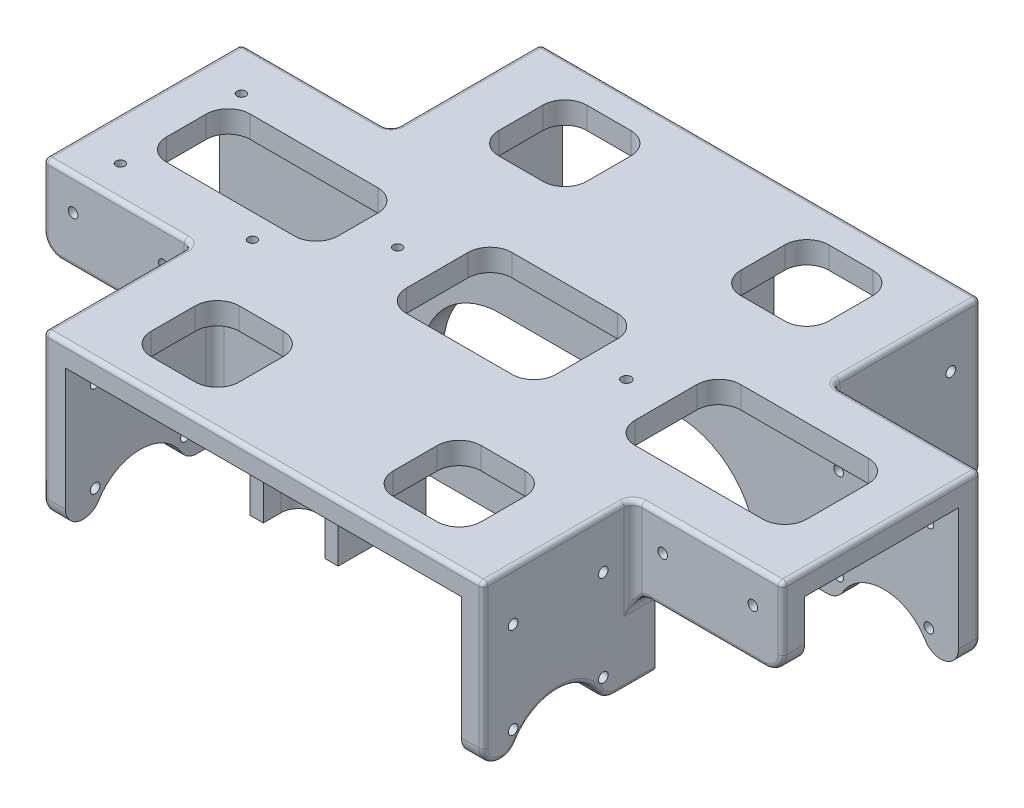
SolidWorks part; units mm, degrees
material "ABS"
ref_plane "Front Plane" through (0, 0, 0) normal (0, 0, 1) x (1, 0, 0)
ref_plane "Top Plane" through (0, 0, 0) normal (0, 1, 0) x (1, 0, 0)
ref_plane "Right Plane" through (0, 0, 0) normal (1, 0, 0) x (0, 0, -1)
sketch "Sketch1" plane through (0, 0, 0) normal (0, 1, 0) x (1, 0, 0)
  line L0 (-84, 0) -> (84, 0)
  line L5 (84, 0) -> (84, 5)
  line L6 (84, 5) -> (50, 5)
  line L7 (50, 5) -> (50, 39)
  line L8 (50, 39) -> (45, 39)
  line L9 (45, 39) -> (45, 5)
  line L10 (45, 5) -> (-45, 5)
  line L11 (-45, 5) -> (-45, 39)
  line L12 (-45, 39) -> (-50, 39)
  line L13 (-50, 39) -> (-50, 5)
  line L14 (-50, 5) -> (-84, 5)
  line L15 (-84, 5) -> (-84, 0)
  line L16 (-50, -74) -> (-50, -40)
  line L17 (-40, -35) -> (50, -35)
  line L18 (50, -40) -> (50, -74)
  line L19 (50, -74) -> (45, -74)
  line L20 (45, -74) -> (45, -40)
  line L21 (45, -40) -> (-45, -40)
  line L22 (-45, -40) -> (-45, -74)
  line L23 (-45, -74) -> (-50, -74)
  line L24 (-40, -35) -> (-84, -35)
  line L25 (-84, -35) -> (-84, -40)
  line L26 (-84, -40) -> (-50, -40)
  line L27 (50, -35) -> (84, -35)
  line L28 (84, -35) -> (84, -40)
  line L29 (84, -40) -> (50, -40)
  dimension "D1" = 5
  dimension "D2" = 90
  dimension "D3" = 34
  dimension "D4" = 34
  dimension "D5" = 5
  dimension "D6" = 5
  dimension "D7" = 5
  dimension "D8" = 5
  dimension "D9" = 34
  dimension "D10" = 34
  dimension "D11" = 5
  dimension "D12" = 34
  dimension "D13" = 5
  dimension "D14" = 90
  dimension "D15" = 35
  dimension "D16" = 34
  dimension "D17" = 34
  dimension "D18" = 34
extrude "Boss-Extrude3" add sketch "Sketch1" along normal blind 31.8
sketch "Sketch6" plane through (-50, 0, 0) normal (-1, 0, 0) x (0, 0, 1)
  line L0 (17.5, 50.2028) -> (17.5, -29.6214) construction
  line L1 (-22, -21.2285) -> (-22, 48.7432) construction
  line L2 (-52.3201, 17) -> (81.6934, 17) construction
  line L3 (-32.3501, 0) -> (-11.6499, 0)
  line L4 (-39, 0) -> (-5, 0) construction
  line L5 (-5, 31.8) -> (-5, 0) construction
  line L6 (0, 31.8) -> (0, 0) construction
  line L7 (67.3501, 0) -> (46.6499, 0)
  circle A0 centre (-32.25, 25.475) radius 1.1
  circle A3 centre (-32.25, 4.775) radius 1.1
  arc A10 (-32.3501, 0) -> (-11.6499, 0) centre (-22, -3.725) cw
  arc A11 (67.3501, 0) -> (46.6499, 0) centre (57, -3.725) ccw
  circle A12 centre (-11.75, 4.775) radius 1.1
  circle A13 centre (-11.75, 25.475) radius 1.1
  circle A14 centre (46.75, 4.775) radius 1.1
  circle A15 centre (46.75, 25.475) radius 1.1
  circle A16 centre (67.25, 25.475) radius 1.1
  circle A17 centre (67.25, 4.775) radius 1.1
  dimension "D1" = 2.2
  dimension "D2" = 12.225
  dimension "D3" = 8.475
  dimension "D8" = 8.5
  dimension "D7" = 11
  dimension "D11" = 2.2
  dimension "D4" = 17
  dimension "D5" = 17
  dimension "D6" = 17.5
  dimension "D9" = 20.5
  dimension "D10" = 20.5
extrude "Cut-Extrude2" cut sketch "Sketch6" against normal through all
sketch "Sketch9" plane through (0, 31.8, 0) normal (0, 1, 0) x (1, 0, 0)
  line L0 (0, 5) -> (0, 0) construction
  line L17 (-45, 39) -> (45, 39)
  line L23 (-45, -40) -> (45, -40) construction
  line L25 (45, -74) -> (-45, -74)
  line L35 (0, -35.0898) -> (0, -40) construction
  line L36 (0, -74) -> (0, -88.5709) construction
  line L37 (-50, 39) -> (-45, 39)
  line L38 (45, 39) -> (50, 39)
  line L39 (-84, 5) -> (-84, 0)
  line L40 (-50, -74) -> (-45, -74)
  line L41 (45, -74) -> (50, -74)
  line L42 (84, 0) -> (84, 5)
  line L43 (-84, 0) -> (-84, -40)
  line L47 (84, 0) -> (84, -40)
  line L49 (-50, 39) -> (-50, 5)
  line L50 (-50, 5) -> (-84, 5)
  line L51 (-84, -40) -> (-50, -40)
  line L52 (-50, -40) -> (-50, -74)
  line L53 (50, -74) -> (50, -40)
  line L54 (50, -40) -> (84, -40)
  line L55 (84, 5) -> (50, 5)
  line L56 (50, 5) -> (50, 39)
extrude "Boss-Extrude5" add sketch "Sketch9" along normal blind 5
sketch "Sketch18" plane through (0, 0, 40) normal (0, 0, 1) x (1, 0, 0)
  line L0 (-84, 0) -> (-84, 18.4)
  line L1 (-84, 36.8) -> (-84, 0) construction
  line L2 (-84, 18.4) -> (-50, 18.4)
  line L3 (-50, 36.8) -> (-50, 0) construction
  line L4 (-50, 18.4) -> (-50, 0)
  line L5 (-50, 0) -> (-84, 0)
  line L6 (50, 0) -> (50, 18.4)
  line L7 (50, 36.8) -> (50, 0) construction
  line L8 (50, 18.4) -> (84, 18.4)
  line L9 (84, 36.8) -> (84, 0) construction
  line L10 (84, 18.4) -> (84, 0)
  line L11 (84, 0) -> (50, 0)
extrude "Cut-Extrude6" cut sketch "Sketch18" against normal blind 10
sketch "Sketch7" plane through (0, 0, -5) normal (0, 0, -1) x (-1, 0, 0)
  line L0 (0, 73.1481) -> (0, -54.2695) construction
  line L1 (-67, -37.1805) -> (-67, 67.9015) construction
  line L2 (-84, 36.8) -> (-84, 0) construction
  line L3 (-110.062, 17) -> (103.6114, 17) construction
  line L4 (-84, 0) -> (-50, 0) construction
  line L5 (-67, 71.1805) -> (-67, -33.9015) construction
  line L8 (-77.3501, 0) -> (-56.6499, 0)
  line L9 (77.3501, 0) -> (56.6499, 0)
  circle A3 centre (-77.25, 4.775) radius 1.1
  arc A10 (-77.3501, 0) -> (-56.6499, 0) centre (-67, -3.725) cw
  arc A11 (77.3501, 0) -> (56.6499, 0) centre (67, -3.725) ccw
  circle A12 centre (-77.25, 25.475) radius 1.1
  circle A13 centre (-56.75, 25.475) radius 1.1
  circle A14 centre (-56.75, 4.775) radius 1.1
  circle A15 centre (56.75, 4.775) radius 1.1
  circle A16 centre (77.25, 4.775) radius 1.1
  circle A17 centre (56.75, 25.475) radius 1.1
  circle A18 centre (77.25, 25.475) radius 1.1
  dimension "D3" = 2.2
  dimension "D5" = 12.225
  dimension "D6" = 11
  dimension "D8" = 10.25
  dimension "D9" = 10.25
  dimension "D10" = 2.2
  dimension "D1" = 17
  dimension "D2" = 17
  dimension "D4" = 8.475
  dimension "D7" = 8.5
sketch "Sketch19" plane through (0, 36.8, 0) normal (0, 1, 0) x (1, 0, 0)
  circle A0 centre (-26, -17.5) radius 1
  circle A1 centre (26, -17.5) radius 1.1
  dimension "D1" = 26
  dimension "D2" = 26
  dimension "D3" = 2
  dimension "D4" = 2.2
  dimension "D5" = 17.5
  dimension "D6" = 17.5
extrude "Cut-Extrude7" cut sketch "Sketch19" against normal blind 10
sketch "Sketch20" plane through (0, 31.8, 0) normal (0, -1, 0) x (1, 0, 0)
  line L0 (-84, 0) -> (84, 0) construction
  line L1 (-84, 0) -> (-84, 35) construction
  circle A0 centre (-74, 32.5) radius 1
  circle A1 centre (-74, 5) radius 1
  circle A2 centre (-44, 32.5) radius 1
  dimension "D1" = 30
  dimension "D2" = 27.5
  dimension "D3" = 2
  dimension "D4" = 2
  dimension "D5" = 2
  dimension "D6" = 5
  dimension "D7" = 10
  dimension "D8" = 10
  dimension "D9" = 27.5
extrude "Cut-Extrude8" cut sketch "Sketch20" against normal blind 10
extrude "Cut-Extrude9" cut sketch "Sketch7" against normal blind 10
sketch "Sketch21" plane through (0, 0, 40) normal (0, 0, 1) x (1, 0, 0)
  line L0 (-67, 62.4596) -> (-67, -41.6657) construction
  line L1 (0, 68.3238) -> (0, -51.3917) construction
  line L3 (-101.9799, 17) -> (93.8272, 17) construction
  line L4 (-84, 0) -> (-77.3501, 0) construction
  circle A0 centre (-77.25, 29.225) radius 1.1
  circle A1 centre (-56.75, 29.225) radius 1.1
  circle A2 centre (56.75, 29.225) radius 1.1
  circle A3 centre (77.25, 29.225) radius 1.1
  dimension "D1" = 2.2
  dimension "D2" = 12.225
  dimension "D3" = 17
  dimension "D4" = 20.5
  dimension "D5" = 17
extrude "Cut-Extrude10" cut sketch "Sketch21" against normal blind 10
sketch "Sketch23" plane through (0, 31.8, 0) normal (0, -1, 0) x (1, 0, 0)
  line L0 (-45, 74) -> (45, 74) construction
  line L1 (-7, 59) -> (7, 59)
  line L2 (-7, 59) -> (-7, 55)
  line L3 (-7, 55) -> (7, 55)
  line L4 (7, 59) -> (7, 55)
  line L5 (-7, 67) -> (-10, 67)
  line L6 (-7, 67) -> (-7, 47)
  line L7 (-7, 47) -> (-10, 47)
  line L8 (-10, 67) -> (-10, 47)
  line L9 (7, 67) -> (10, 67)
  line L10 (7, 67) -> (7, 47)
  line L11 (7, 47) -> (10, 47)
  line L12 (10, 67) -> (10, 47)
  line L13 (0, -20.24) -> (0, 20.24) construction
  line L14 (-84, 17.5) -> (84, 17.5) construction
  line L15 (-84, 0) -> (-84, 35) construction
  line L16 (84, 35) -> (84, 0) construction
  line L17 (7, -12) -> (10, -12)
  line L18 (10, -32) -> (10, -12)
  line L19 (7, -32) -> (10, -32)
  line L20 (7, -32) -> (7, -12)
  line L21 (-7, -20) -> (7, -20)
  line L22 (7, -24) -> (7, -20)
  line L23 (-7, -24) -> (7, -24)
  line L24 (-7, -24) -> (-7, -20)
  line L25 (-7, -12) -> (-10, -12)
  line L26 (-10, -32) -> (-10, -12)
  line L27 (-7, -32) -> (-10, -32)
  line L28 (-7, -32) -> (-7, -12)
  point P14 (0, 55)
  dimension "D1" = 20
  dimension "D2" = 3
  dimension "D3" = 0
  dimension "D4" = 0
  dimension "D5" = 20
  dimension "D6" = 3
  dimension "D7" = 4
  dimension "D8" = 8
  dimension "D9" = 7
  dimension "D10" = 7
  dimension "D11" = 20
extrude "Boss-Extrude6" add sketch "Sketch23" along normal blind 15 contours L5 L8 L7 L6 L2 | L4 L1 L2 L3 | L12 L9 L10 L4 L11 | L27 L28 L24 L25 L26 | L24 L23 L20 L21 | L20 L19 L18 L17 region at (0, 31.8, 57) region at (-8.5, 31.8, 57) region at (8.5, 31.8, 57) region at (8.5, 31.8, -22) region at (0, 31.8, -22) region at (-8.5, 31.8, -22)
sketch "Sketch24" plane through (0, 0, 40) normal (0, 0, 1) x (1, 0, 0)
  line L0 (-20, 0) -> (20, 0) construction
  line L1 (-45, 0) -> (45, 0) construction
  line L2 (-20, 18) -> (20, 18)
  line L3 (-20, -18) -> (20, -18)
  arc A0 (-20, 18) -> (-20, -18) centre (-20, 0) ccw
  arc A1 (20, -18) -> (20, 18) centre (20, 0) ccw
  point P4 (0, 0)
  dimension "D1" = 40
  dimension "D2" = 18
extrude "Cut-Extrude11" cut sketch "Sketch24" against normal blind 46
sketch "Sketch25" plane through (0, 31.8, 0) normal (0, -1, 0) x (1, 0, 0)
  line L0 (-84, 0) -> (-84, 35) construction
  line L1 (-12, 29.5) -> (12, 29.5)
  line L2 (-17, 24.5) -> (-17, 10.5)
  line L3 (-12, 5.5) -> (12, 5.5)
  line L4 (17, 24.5) -> (17, 10.5)
  line L5 (40, 29.5) -> (69, 29.5)
  line L6 (35, 24.5) -> (35, 10.5)
  line L7 (40, 5.5) -> (69, 5.5)
  line L8 (74, 24.5) -> (74, 10.5)
  line L9 (-69, 27) -> (-40, 27)
  line L10 (-74, 22) -> (-74, 13)
  line L11 (-69, 8) -> (-40, 8)
  line L12 (-35, 22) -> (-35, 13)
  line L13 (-32.5, 67) -> (-22.5, 67)
  line L14 (-37.5, 62) -> (-37.5, 52)
  line L15 (-32.5, 47) -> (-22.5, 47)
  line L16 (-17.5, 62) -> (-17.5, 52)
  line L17 (22.5, 67) -> (32.5, 67)
  line L18 (17.5, 62) -> (17.5, 52)
  line L19 (22.5, 47) -> (32.5, 47)
  line L20 (37.5, 62) -> (37.5, 52)
  line L21 (-32.5, -12) -> (-22.5, -12)
  line L22 (-37.5, -17) -> (-37.5, -27)
  line L23 (-32.5, -32) -> (-22.5, -32)
  line L24 (-17.5, -17) -> (-17.5, -27)
  line L25 (22.5, -12) -> (32.5, -12)
  line L26 (17.5, -17) -> (17.5, -27)
  line L27 (22.5, -32) -> (32.5, -32)
  line L28 (37.5, -17) -> (37.5, -27)
  line L29 (84, 35) -> (-84, 35) construction
  line L30 (-56.6499, 0) -> (-77.3501, 0) construction
  line L32 (84, 35) -> (84, 0) construction
  line L33 (-45, 74) -> (45, 74) construction
  line L34 (-10, 67) -> (-10, 47) construction
  line L35 (10, 67) -> (10, 47) construction
  line L36 (-10, -32) -> (-10, -12) construction
  line L37 (10, -12) -> (10, -20) construction
  line L38 (45, -39) -> (-45, -39) construction
  arc A0 (22.5, -32) -> (17.5, -27) centre (22.5, -27) cw
  arc A1 (32.5, -32) -> (37.5, -27) centre (32.5, -27) ccw
  arc A2 (37.5, -17) -> (32.5, -12) centre (32.5, -17) ccw
  arc A3 (17.5, -17) -> (22.5, -12) centre (22.5, -17) cw
  arc A4 (-32.5, -32) -> (-37.5, -27) centre (-32.5, -27) cw
  arc A5 (-22.5, -32) -> (-17.5, -27) centre (-22.5, -27) ccw
  arc A6 (-17.5, -17) -> (-22.5, -12) centre (-22.5, -17) ccw
  arc A7 (-37.5, -17) -> (-32.5, -12) centre (-32.5, -17) cw
  arc A8 (-40, 8) -> (-35, 13) centre (-40, 13) ccw
  arc A9 (-74, 13) -> (-69, 8) centre (-69, 13) ccw
  arc A10 (-74, 22) -> (-69, 27) centre (-69, 22) cw
  arc A11 (-40, 27) -> (-35, 22) centre (-40, 22) cw
  arc A12 (-17, 10.5) -> (-12, 5.5) centre (-12, 10.5) ccw
  arc A13 (-17, 24.5) -> (-12, 29.5) centre (-12, 24.5) cw
  arc A14 (12, 5.5) -> (17, 10.5) centre (12, 10.5) ccw
  arc A15 (17, 24.5) -> (12, 29.5) centre (12, 24.5) ccw
  arc A16 (40, 5.5) -> (35, 10.5) centre (40, 10.5) cw
  arc A17 (69, 5.5) -> (74, 10.5) centre (69, 10.5) ccw
  arc A18 (74, 24.5) -> (69, 29.5) centre (69, 24.5) ccw
  arc A19 (35, 24.5) -> (40, 29.5) centre (40, 24.5) cw
  arc A20 (22.5, 47) -> (17.5, 52) centre (22.5, 52) cw
  arc A21 (32.5, 47) -> (37.5, 52) centre (32.5, 52) ccw
  arc A22 (37.5, 62) -> (32.5, 67) centre (32.5, 62) ccw
  arc A23 (17.5, 62) -> (22.5, 67) centre (22.5, 62) cw
  arc A24 (-32.5, 47) -> (-37.5, 52) centre (-32.5, 52) cw
  arc A25 (-17.5, 52) -> (-22.5, 47) centre (-22.5, 52) cw
  arc A26 (-17.5, 62) -> (-22.5, 67) centre (-22.5, 62) ccw
  arc A27 (-37.5, 62) -> (-32.5, 67) centre (-32.5, 62) cw
  point P53 (37.5, -32)
  point P56 (37.5, -12)
  point P61 (-37.5, -32)
  point P64 (-17.5, -32)
  point P67 (-17.5, -12)
  point P80 (-17, 5.5)
  point P83 (-17, 29.5)
  point P90 (35, 5.5)
  point P97 (35, 29.5)
  point P100 (17.5, 47)
  point P107 (17.5, 67)
  point P110 (-37.5, 47)
  point P115 (-17.5, 67)
  point P118 (-37.5, 67)
  dimension "D29" = 5
  dimension "D1" = 10
  dimension "D2" = 8
  dimension "D3" = 8
  dimension "D4" = 24
  dimension "D5" = 34
  dimension "D6" = 17
  dimension "D7" = 5.5
  dimension "D8" = 5.5
  dimension "D9" = 24
  dimension "D10" = 10
  dimension "D11" = 18
  dimension "D12" = 18
  dimension "D13" = 20
  dimension "D14" = 20
  dimension "D15" = 7
  dimension "D16" = 7.5
  dimension "D17" = 20
  dimension "D18" = 20
  dimension "D19" = 7.5
  dimension "D20" = 7
  dimension "D21" = 20
  dimension "D22" = 20
  dimension "D23" = 7.5
  dimension "D24" = 7.5
  dimension "D25" = 20
  dimension "D26" = 20
  dimension "D27" = 7
  dimension "D28" = 7
extrude "Cut-Extrude12" cut sketch "Sketch25" against normal blind 60
fillet "Fillet1" radius 4 26 edges at (-38, 0, 37.5) (50, 18.4, 37.5) (-50, 18.4, 37.5) (-47.5, 0, -39) (-47.5, 0, -32.3501) (-47.5, 0, -11.6499) (-47.5, 0, 74) (-47.5, 0, 67.3501) (-47.5, 0, 46.6499) (84, 18.4, 37.5) (47.5, 0, 74) (47.5, 0, 67.3501) (47.5, 0, 46.6499) (38, 0, 37.5) (-84, 18.4, 37.5) (-84, 0, -2.5) (-77.3501, 0, -2.5) (-56.6499, 0, -2.5) (-38, 0, -2.5) (38, 0, -2.5) (84, 0, -2.5) (77.3501, 0, -2.5) (56.6499, 0, -2.5) (47.5, 0, -39) (47.5, 0, -32.3501) (47.5, 0, -11.6499)
fillet "Fillet2" radius 4 8 edges at (7, 24.3, 59) (-7, 24.3, 59) (-7, 24.3, 55) (7, 24.3, 55) (-7, 24.3, -20) (7, 24.3, -20) (-7, 24.3, -24) (7, 24.3, -24)
fillet "Fillet4" radius 2 8 edges at (45, 15.9, 40) (50, 25.6, 40) (-45, 15.9, 40) (-50, 25.6, 40) (-50, 18.4, -5) (-45, 15.9, -5) (45, 15.9, -5) (50, 18.4, -5)
fillet "Fillet6" radius 1 54 edges at (-50, 0, 39.5711) (-50, 0.5186, 46.1119) (-50, 7.275, 57) (-50, 0.5186, 67.8881) (-50, 0, 69.9289) (-50, 1.1716, 72.8284) (-50, 20.4, 74) (-50.52, 16.3722, 40.6548) (-52.9647, 18.2637, 40) (-67, 18.4, 40) (-82.8284, 19.5716, 40) (-84, 29.6, 40) (50, 0, 39.5711) (50, 0.5186, 46.1119) (50, 7.275, 57) (50, 0.5186, 67.8881) (50, 0, 69.9289) (50, 1.1716, 72.8284) (50.52, 16.3722, 40.6548) (52.9647, 18.2637, 40) (67, 18.4, 40) (82.8284, 19.5716, 40) (84, 20.4, -5) (82.8284, 1.1716, -5) (79.9289, 0, -5) (77.8881, 0.5186, -5) (67, 7.275, -5) (56.1119, 0.5186, -5) (53.0711, 0, -5) (50.5858, 0, -5.5858) (50, 0, -8.0711) (50, 0.5186, -11.1119) (50, 7.275, -22) (50, 0.5186, -32.8881) (50, 0, -34.9289) (50, 1.1716, -37.8284) (-50, 20.4, -39) (-50, 1.1716, -37.8284) (-50, 0, -34.9289) (-50, 0.5186, -32.8881) (-50, 7.275, -22) (-50, 0.5186, -11.1119) (-50, 0, -8.0711) (-50.5858, 0, -5.5858) (-53.0711, 0, -5) (-56.1119, 0.5186, -5) (-67, 7.275, -5) (-77.8881, 0.5186, -5) (-79.9289, 0, -5) (-82.8284, 1.1716, -5) (50, 20.4, 74) (84, 29.6, 40) (50, 20.4, -39) (-84, 20.4, -5)
fillet "Fillet7" radius 1 24 edges at (83.7071, 36.8, 39.7071) (67.5, 36.8, 40) (50.5858, 36.8, 40.5858) (50, 36.8, 57.5) (49.7071, 36.8, 73.7071) (0, 36.8, 74) (-49.7071, 36.8, 73.7071) (-50, 36.8, 57.5) (-50.5858, 36.8, 40.5858) (-67.5, 36.8, 40) (-83.7071, 36.8, 39.7071) (-84, 36.8, 17.5) (-83.7071, 36.8, -4.7071) (-67.5, 36.8, -5) (-50.5858, 36.8, -5.5858) (-50, 36.8, -22.5) (-49.7071, 36.8, -38.7071) (0, 36.8, -39) (49.7071, 36.8, -38.7071) (50, 36.8, -22.5) (50.5858, 36.8, -5.5858) (67.5, 36.8, -5) (83.7071, 36.8, -4.7071) (84, 36.8, 17.5)
ref_plane "Plane1" through (0, 0, 17.5) normal (0, 0, 1) x (1, 0, 0)
ref_plane "Plane2" through (0, 0, 0) normal (1, 0, 0) x (0, 0, -1)
ref_plane "Plane3" through (0, 36.8, 0) normal (0, 1, 0) x (1, 0, 0)
sketch "Sketch27" plane through (0, 36.8, 0) normal (0, 1, 0) x (1, 0, 0)
  line L0 (0, -20.24) -> (0, 20.24) construction
  line L1 (-20.24, -17.5) -> (20.24, -17.5) construction
  point P0 (0, -17.5)
